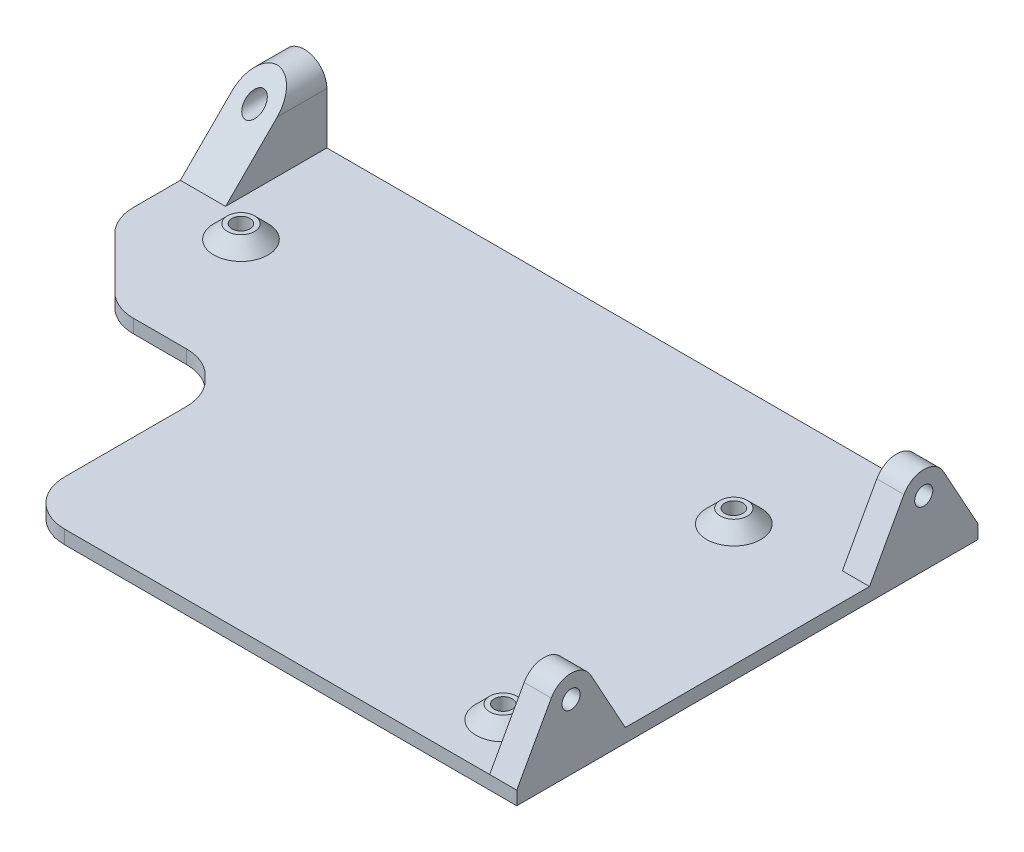
SolidWorks part; units mm, degrees
ref_plane "Front Plane" through (0, 0, 0) normal (0, 0, 1) x (1, 0, 0)
ref_plane "Top Plane" through (0, 0, 0) normal (0, 1, 0) x (1, 0, 0)
ref_plane "Right Plane" through (0, 0, 0) normal (1, 0, 0) x (0, 0, -1)
sketch "Sketch1" plane through (0, 0, 0) normal (0, 1, 0) x (1, 0, 0)
  line L1 (-120.5517, 19.2041) -> (-109.309, 7.9615)
  line L2 (-102.238, 5.0326) -> (-90.5222, 5.0326)
  line L3 (-83.4512, 2.1036) -> (-82.4095, 1.062)
  line L4 (-79.4806, -6.0091) -> (-79.4806, -32.9674)
  line L5 (-69.4806, -42.9674) -> (30.5194, -42.9674)
  line L6 (30.5194, -42.9674) -> (30.5194, 57.0326)
  line L7 (23.5194, 59.0326) -> (-123.4806, 59.0326)
  line L9 (23.5194, -35.9674) -> (23.5194, 57.0326)
  line L10 (-72.4806, -35.9674) -> (23.5194, -35.9674)
  line L11 (-72.4806, 1.0326) -> (-72.4806, -35.9674)
  line L12 (-83.4806, 12.0326) -> (-72.4806, 1.0326)
  line L13 (-103.4806, 12.0326) -> (-83.4806, 12.0326)
  line L14 (-112.4806, 21.0326) -> (-103.4806, 12.0326)
  line L15 (-112.4806, 57.0326) -> (-112.4806, 21.0326)
  line L16 (23.5194, 57.0326) -> (-112.4806, 57.0326)
  line L17 (23.5194, -35.9674) -> (23.5194, 57.0326) construction
  line L18 (-72.4806, -35.9674) -> (23.5194, -35.9674) construction
  line L19 (-72.4806, 1.0326) -> (-72.4806, -35.9674) construction
  line L20 (-83.4806, 12.0326) -> (-72.4806, 1.0326) construction
  line L21 (-103.4806, 12.0326) -> (-83.4806, 12.0326) construction
  line L22 (-112.4806, 21.0326) -> (-103.4806, 12.0326) construction
  line L23 (-112.4806, 57.0326) -> (-112.4806, 21.0326) construction
  line L24 (23.5194, 57.0326) -> (-112.4806, 57.0326) construction
  line L26 (23.5194, 59.0326) -> (30.5194, 59.0326)
  line L27 (30.5194, 59.0326) -> (30.5194, 57.0326)
  line L28 (-119.4806, 18.1331) -> (-106.3801, 5.0326) construction
  line L29 (-123.4806, 57.0326) -> (-123.4806, 21.0326) construction
  line L30 (-123.4806, 57.0326) -> (-123.4806, 59.0326)
  line L31 (23.5194, 59.0326) -> (-112.4806, 59.0326) construction
  line L32 (-106.3801, 5.0326) -> (-86.3801, 5.0326) construction
  line L33 (-86.3801, 5.0326) -> (-79.4806, -1.8669) construction
  line L34 (-79.4806, -1.8669) -> (-79.4806, -42.9674) construction
  line L35 (-79.4806, -42.9674) -> (30.5194, -42.9674) construction
  line L36 (-119.4806, 57.0326) -> (-119.4806, 18.1331) construction
  line L37 (-123.4806, 57.0326) -> (-123.4806, 26.2752)
  circle A0 centre (-105.4806, 32.0326) radius 1.5 construction
  circle A1 centre (3.5194, 32.0326) radius 1.5 construction
  circle A2 centre (15.5194, -30.9674) radius 2.5 construction
  circle A3 centre (-105.4806, 32.0326) radius 1.5 construction
  circle A4 centre (3.5194, 32.0326) radius 1.5 construction
  circle A5 centre (15.5194, -30.9674) radius 2.5 construction
  circle A6 centre (-105.4806, 32.0326) radius 2
  circle A7 centre (3.5194, 32.0326) radius 2
  circle A8 centre (15.5194, -30.9674) radius 2
  arc A9 (-120.5517, 19.2041) -> (-123.4806, 26.2752) centre (-113.4806, 26.2752) cw
  arc A10 (-109.309, 7.9615) -> (-102.238, 5.0326) centre (-102.238, 15.0326) ccw
  arc A11 (-90.5222, 5.0326) -> (-83.4512, 2.1036) centre (-90.5222, -4.9674) cw
  arc A12 (-82.4095, 1.062) -> (-79.4806, -6.0091) centre (-89.4806, -6.0091) cw
  arc A13 (-79.4806, -32.9674) -> (-69.4806, -42.9674) centre (-69.4806, -32.9674) ccw
  dimension "D4" = 4
  dimension "D5" = 4
  dimension "D6" = 4
  dimension "D8" = 10
  dimension "D1" = 0
  dimension "D2" = 7
  dimension "D3" = 2
  dimension "D7" = 11
extrude "Boss-Extrude1" add sketch "Sketch1" along normal blind 3
sketch "Sketch4" plane through (0, 3, 0) normal (0, 1, 0) x (1, 0, 0)
  circle A0 centre (-105.4806, 32.0326) radius 3
  circle A1 centre (3.5194, 32.0326) radius 3
  circle A2 centre (15.5194, -30.9674) radius 3
  circle A3 centre (15.5194, -30.9674) radius 2 construction
  circle A4 centre (3.5194, 32.0326) radius 2 construction
  circle A5 centre (-105.4806, 32.0326) radius 2 construction
  circle A6 centre (15.5194, -30.9674) radius 2
  circle A7 centre (3.5194, 32.0326) radius 2
  circle A8 centre (-105.4806, 32.0326) radius 2
  circle M10 centre (-105.4806, 32.0326) radius 2
  circle M11 centre (3.5194, 32.0326) radius 2
  circle M12 centre (15.5194, -30.9674) radius 2
  dimension "D1" = 6
  dimension "D2" = 6
  dimension "D3" = 6
extrude "Boss-Extrude2" add sketch "Sketch4" along normal blind 3 contours A0 M10 | A2 M12 | A1 M11 region at (-108.3957, 3, -32.0326) region at (0.6043, 3, -32.0326) region at (12.6043, 3, 30.9674)
chamfer "Chamfer1" distance 3 angle 45 3 edges at (15.5194, 3, 27.9674) (3.5194, 3, -35.0326) (-105.4806, 3, -35.0326)
sketch "Sketch7" plane through (0, 0, -59.0326) normal (0, 0, -1) x (-1, 0, 0)
  line L0 (51.9806, 14.4) -> (118.4806, 14.4) construction
  line L1 (-5.5194, 21.2) -> (109.4806, 7.6) construction
  line L2 (109.4806, 21.2) -> (-5.5194, 7.6) construction
  line L12 (-5.5194, 7.6) -> (109.4806, 7.6)
  line L13 (109.4806, 7.6) -> (109.4806, 21.2)
  line L14 (109.4806, 21.2) -> (-5.5194, 21.2)
  line L15 (-5.5194, 21.2) -> (-5.5194, 7.6)
  line L16 (-5.5194, 7.6) -> (109.4806, 7.6) construction
  line L17 (109.4806, 7.6) -> (109.4806, 21.2) construction
  line L18 (109.4806, 21.2) -> (-5.5194, 21.2) construction
  line L19 (-5.5194, 21.2) -> (-5.5194, 7.6) construction
  line L20 (113.4806, 14.4) -> (113.4806, 3)
  line L21 (113.4806, 3) -> (123.4806, 3)
  line L22 (123.4806, 3) -> (123.4806, 14.4)
  arc A1 (123.4806, 14.4) -> (113.4806, 14.4) centre (118.4806, 14.4) ccw
  point P0 (0, 0)
  point P11 (51.9806, 14.4)
  dimension "D3" = 4
  dimension "D2" = 0
extrude "Boss-Extrude3" add sketch "Sketch7" against normal blind 4
sketch "Sketch9" plane through (0, 0, -55.0326) normal (0, 0, 1) x (1, 0, 0)
  line L10 (-123.4806, 3) -> (-113.4806, 3)
  line L11 (-113.4806, 3) -> (-113.4806, 14.4)
  line L12 (-123.4806, 14.4) -> (-123.4806, 3)
  line L13 (-123.4806, 3) -> (-113.4806, 3)
  line L14 (-113.4806, 3) -> (-113.4806, 14.4)
  line L15 (-123.4806, 14.4) -> (-123.4806, 3)
  arc A3 (-113.4806, 14.4) -> (-123.4806, 14.4) centre (-118.4806, 14.4) ccw
  arc A4 (-113.4806, 14.4) -> (-123.4806, 14.4) centre (-118.4806, 14.4) ccw
  dimension "D1" = 0
extrude "Boss-Extrude4" add sketch "Sketch9" along normal blind 20
sketch "Sketch10" plane through (-123.4806, 0, 0) normal (-1, 0, 0) x (0, 0, 1)
  line L0 (-53.0326, 19.4) -> (-36.6326, 3)
  line L1 (-35.0326, 19.4) -> (-59.0326, 19.4) construction
  line L2 (-36.6326, 3) -> (-35.0326, 3)
  line L3 (-53.0326, 19.4) -> (-35.0326, 19.4)
  line L4 (-35.0326, 19.4) -> (-35.0326, 3)
  dimension "D1" = 135
  dimension "D2" = 6
extrude "Cut-Extrude1" cut sketch "Sketch10" against normal up to next
sketch "Sketch11" plane through (0, 0, -59.0326) normal (0, 0, -1) x (-1, 0, 0)
  point P7 (118.4806, 14.4)
  point P13 (0, 0)
hole_wizard "Ø4.0mm Dowel Hole1" positions "Sketch11" profile "Sketch12" hole size "Ø4.0" standard "ANSI Metric" end condition through all
sketch "Sketch12" plane through (-118.4806, 14.4, -59.0326) normal (1, 0, 0) x (0, 1, 0)
  line L0 (0, 0) -> (0, 102)
  line L1 (0, 102) -> (2, 102)
  line L2 (2, 102) -> (2, 0.025)
  line L3 (2, 0.025) -> (2.025, 0)
  line L5 (2.025, 0) -> (0, 0)
  line L6 (-2, 0.025) -> (-2.025, 0) construction
  line L11 (0, -6.35) -> (0, 107.95) construction
  dimension "Thru Hole Dia." = 4
  dimension "Thru Hole Depth" = 102
  dimension "Near C'Sink Dia." = 4.05
  dimension "Near C'Sink Angle" = 90
sketch "Sketch13" plane through (30.5194, 0, 0) normal (1, 0, 0) x (0, 0, -1)
  line L0 (64.0326, 19.4) -> (-49935.9674, 19.4) construction
  line L1 (56.4505, 14.4) -> (-49943.5495, 14.4) construction
  line L2 (-26.5895, 16.8153) -> (-18.9674, 3)
  line L3 (48.0326, 14.4) -> (59.0326, 14.4) construction
  line L4 (-35.9674, 14.4) -> (-35.9674, 3) construction
  line L5 (-42.9674, 3) -> (59.0326, 3) construction
  line L6 (-25.9674, 14.4) -> (-25.9674, 3) construction
  line L7 (-18.9674, 3) -> (-42.9674, 3)
  line L8 (59.0326, 19.4) -> (53.0326, 19.4) construction
  line L9 (-33.9674, 6) -> (-35.9674, 6) construction
  line L10 (-27.9674, 6) -> (-25.9674, 6) construction
  line L11 (-42.9674, 3) -> (-35.3453, 16.8153)
  line L12 (-42.9674, 3) -> (59.0326, 3) construction
  line L13 (8.0326, 24.4808) -> (8.0326, -49975.5192) construction
  line L14 (-42.9674, 3) -> (-42.9674, 0) construction
  line L15 (59.0326, 3) -> (59.0326, 0) construction
  line L16 (44.0326, 6) -> (42.0326, 6) construction
  line L17 (50.0326, 6) -> (52.0326, 6) construction
  line L18 (42.0326, 14.4) -> (42.0326, 3) construction
  line L19 (52.0326, 14.4) -> (52.0326, 3) construction
  line L20 (59.0326, 3) -> (51.4105, 16.8153)
  line L21 (35.0326, 3) -> (59.0326, 3)
  line L22 (42.6547, 16.8153) -> (35.0326, 3)
  circle A1 centre (-30.9674, 14.4) radius 5 construction
  arc A2 (-35.3453, 16.8153) -> (-26.5895, 16.8153) centre (-30.9674, 14.4) cw
  circle A3 centre (-30.9674, 14.4) radius 2
  circle A4 centre (47.0326, 14.4) radius 5 construction
  circle A5 centre (47.0326, 14.4) radius 2
  arc A6 (51.4105, 16.8153) -> (42.6547, 16.8153) centre (47.0326, 14.4) ccw
  point P33 (-30.9674, 3)
  dimension "D2" = 4
extrude "Boss-Extrude5" add sketch "Sketch13" against normal blind 6
